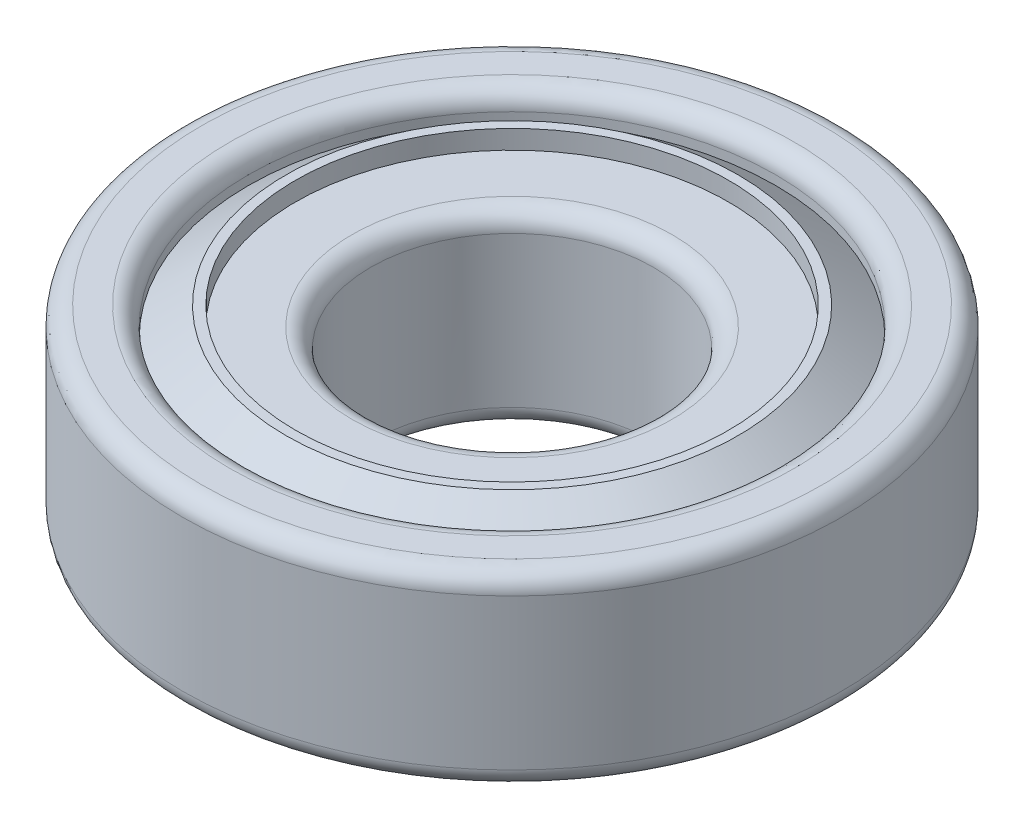
SolidWorks part; units mm, degrees
ref_plane "Alzado" through (0, 0, 0) normal (0, 0, 1) x (1, 0, 0)
ref_plane "Planta" through (0, 0, 0) normal (0, 1, 0) x (1, 0, 0)
ref_plane "Vista lateral" through (0, 0, 0) normal (1, 0, 0) x (0, 0, -1)
sketch "Croquis1" plane through (0, 0, 0) normal (0, 0, 1) x (1, 0, 0)
  line L0 (0, 22.333) -> (0, -19.3286) construction
  line L1 (14, 10) -> (14, 8.5047)
  line L2 (0, 0) -> (17.5, 0)
  line L3 (0, 0) -> (0, 10)
  line L4 (0, 10) -> (17.5, 10)
  line L5 (17.5, 0) -> (17.5, 10)
  line L6 (14, 8.5047) -> (12, 10)
  line L7 (12, 10) -> (11.5, 10)
  line L8 (11.5, 10) -> (11.5, 9)
  line L9 (11.5, 9) -> (7.5, 9)
  line L10 (7.5, 9) -> (7.5, -1)
  line L11 (7.5, -1) -> (12.25, -1)
  line L12 (12.25, -1) -> (12.25, 0)
  dimension "D1" = 17.5
  dimension "D2" = 10
  dimension "D3" = 1
  dimension "D4" = 12.25
  dimension "D5" = 7.5
  dimension "D6" = 1
  dimension "D7" = 3.5
  dimension "D8" = 1.4953
  dimension "D9" = 2
  dimension "D10" = 6
revolve "Revolución1" add sketch "Croquis1" angle 360 about L0 region at (12.6138, 4.7383, 0) region at (9.875, -0.5, 0)
fillet "Redondeo1" radius 1 2 edges at (0, 0, 17.5) (0, 10, 17.5)
fillet "Redondeo2" radius 1 4 edges at (0, -1, 7.5) (0, -1, 12.25) (0, 10, 14) (0, 9, 7.5)
